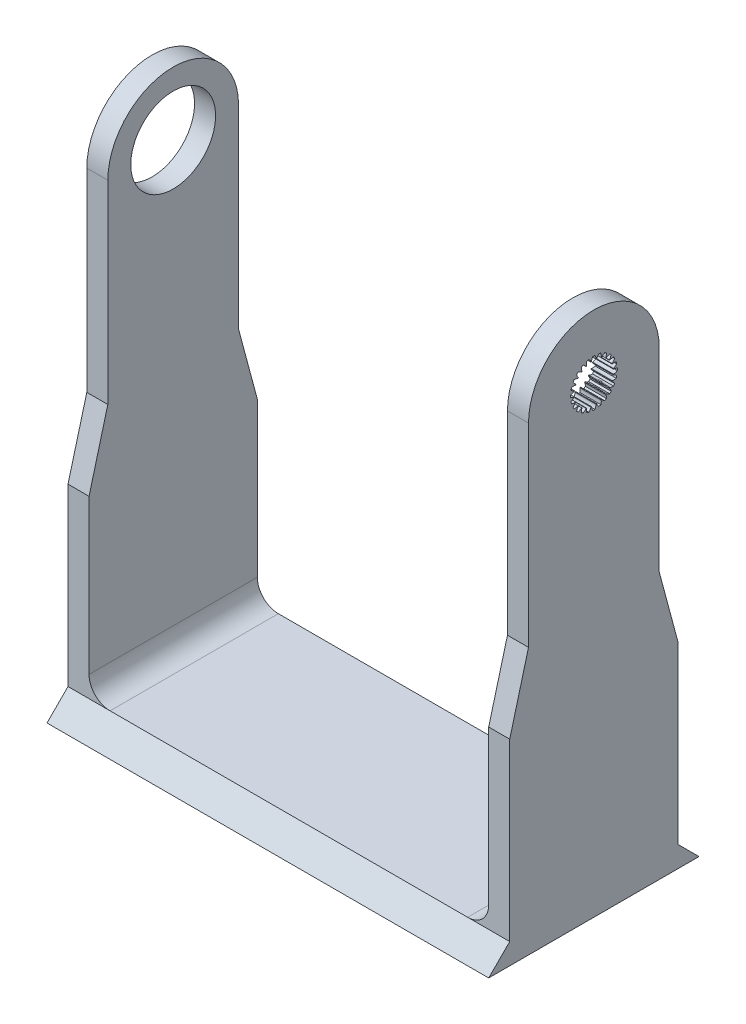
SolidWorks part; units mm, degrees
ref_plane "Front Plane" through (0, 0, 0) normal (0, 0, 1) x (1, 0, 0)
ref_plane "Top Plane" through (0, 0, 0) normal (0, 1, 0) x (1, 0, 0)
ref_plane "Right Plane" through (0, 0, 0) normal (1, 0, 0) x (0, 0, -1)
sketch "Sketch1" plane through (0, 0, 0) normal (0, 1, 0) x (1, 0, 0)
  line L1 (-31.5, -15) -> (31.5, -15)
  line L2 (-31.5, -15) -> (-31.5, 15)
  line L3 (-31.5, 15) -> (31.5, 15)
  line L4 (31.5, -15) -> (31.5, 15)
  point P4 (0, 15)
  point P6 (31.5, 0)
  dimension "D1" = 63
  dimension "D2" = 30
extrude "Boss-Extrude1" add sketch "Sketch1" along normal blind 3
sketch "Sketch2" plane through (0, 3, 0) normal (0, 1, 0) x (1, 0, 0)
  line L0 (-31.5, 15) -> (-31.5, -15) construction
  line L1 (-31.5, -12) -> (-28.5, -12)
  line L2 (-31.5, -12) -> (-31.5, 12)
  line L3 (-31.5, 12) -> (-28.5, 12)
  line L4 (-28.5, -12) -> (-28.5, 12)
  line L5 (31.5, -15) -> (31.5, 15) construction
  line L6 (31.5, -12) -> (28.5, -12)
  line L7 (31.5, -12) -> (31.5, 12)
  line L8 (31.5, 12) -> (28.5, 12)
  line L9 (28.5, -12) -> (28.5, 12)
  line L10 (31.5, 15) -> (-31.5, 15) construction
  line L11 (-31.5, -15) -> (31.5, -15) construction
  dimension "D1" = 3
  dimension "D2" = 3
  dimension "D3" = 3
  dimension "D4" = 3
  dimension "D5" = 3
  dimension "D6" = 3
extrude "Boss-Extrude2" add sketch "Sketch2" along normal blind 75
sketch "Sketch3" plane through (31.5, 0, 0) normal (1, 0, 0) x (0, 0, -1)
  line L0 (-15, 0) -> (15, 0) construction
  line L1 (-12, 78) -> (12, 78) construction
  line L2 (0, 13) -> (12, 13) construction
  line L3 (12, 78) -> (12, 3) construction
  line L4 (0, 13) -> (0, 66) construction
  line B0 (-2.5678, 64.8835) -> (-2.5895, 64.8732)
  line B1 (-2.2706, 64.3209) -> (-2.2508, 64.3345)
  line B2 (-2.1913, 64.257) -> (-2.2096, 64.2413)
  line B3 (-1.7587, 63.7904) -> (-1.743, 63.8087)
  line B4 (-1.6655, 63.7492) -> (-1.6791, 63.7294)
  line B5 (-1.1268, 63.4105) -> (-1.1165, 63.4322)
  line B6 (-1.0262, 63.3948) -> (-1.0342, 63.3722)
  line B7 (-0.4182, 63.2071) -> (-0.4138, 63.2308)
  line B8 (-0.317, 63.218) -> (-0.3189, 63.194)
  line B9 (0.3189, 63.194) -> (0.317, 63.218)
  line B10 (0.4138, 63.2308) -> (0.4182, 63.2071)
  line B11 (1.0342, 63.3722) -> (1.0262, 63.3948)
  line B12 (1.1165, 63.4322) -> (1.1268, 63.4105)
  line B13 (1.6791, 63.7294) -> (1.6655, 63.7492)
  line B14 (1.743, 63.8087) -> (1.7587, 63.7904)
  line B15 (2.2096, 64.2413) -> (2.1913, 64.257)
  line B16 (2.2508, 64.3345) -> (2.2706, 64.3209)
  line B17 (2.5895, 64.8732) -> (2.5678, 64.8835)
  line B18 (2.6052, 64.9738) -> (2.6278, 64.9658)
  line B19 (2.7929, 65.5818) -> (2.7692, 65.5862)
  line B20 (2.782, 65.683) -> (2.806, 65.6811)
  line B21 (2.806, 66.3189) -> (2.782, 66.317)
  line B22 (2.7692, 66.4138) -> (2.7929, 66.4182)
  line B23 (2.6278, 67.0342) -> (2.6052, 67.0262)
  line B24 (2.5678, 67.1165) -> (2.5895, 67.1268)
  line B25 (2.2706, 67.6791) -> (2.2508, 67.6655)
  line B26 (2.1913, 67.743) -> (2.2096, 67.7587)
  line B27 (1.7587, 68.2096) -> (1.743, 68.1913)
  line B28 (1.6655, 68.2508) -> (1.6791, 68.2706)
  line B29 (1.1268, 68.5895) -> (1.1165, 68.5678)
  line B30 (1.0262, 68.6052) -> (1.0342, 68.6278)
  line B31 (0.4182, 68.7929) -> (0.4138, 68.7692)
  line B32 (0.317, 68.782) -> (0.3189, 68.806)
  line B33 (-0.3189, 68.806) -> (-0.317, 68.782)
  line B34 (-0.4138, 68.7692) -> (-0.4182, 68.7929)
  line B35 (-1.0342, 68.6278) -> (-1.0262, 68.6052)
  line B36 (-1.1165, 68.5678) -> (-1.1268, 68.5895)
  line B37 (-1.6791, 68.2706) -> (-1.6655, 68.2508)
  line B38 (-1.743, 68.1913) -> (-1.7587, 68.2096)
  line B39 (-2.2096, 67.7587) -> (-2.1913, 67.743)
  line B40 (-2.2508, 67.6655) -> (-2.2706, 67.6791)
  line B41 (-2.5895, 67.1268) -> (-2.5678, 67.1165)
  line B42 (-2.6052, 67.0262) -> (-2.6278, 67.0342)
  line B43 (-2.7929, 66.4182) -> (-2.7692, 66.4138)
  line B44 (-2.782, 66.317) -> (-2.806, 66.3189)
  line B45 (-2.806, 65.6811) -> (-2.782, 65.683)
  line B46 (-2.7692, 65.5862) -> (-2.7929, 65.5818)
  line B47 (-2.6278, 64.9658) -> (-2.6052, 64.9738)
  arc B48 (-2.6052, 64.9738) -> (-2.5678, 64.8835) centre (0, 66) ccw
  arc B49 (-2.9635, 64.4594) -> (-2.8159, 64.2038) centre (0, 66) ccw
  arc B50 (-2.2508, 64.3345) -> (-2.1913, 64.257) centre (0, 66) ccw
  arc B51 (-2.4638, 63.7449) -> (-2.2551, 63.5362) centre (0, 66) ccw
  arc B52 (-1.743, 63.8087) -> (-1.6655, 63.7492) centre (0, 66) ccw
  arc B53 (-1.7962, 63.1841) -> (-1.5406, 63.0365) centre (0, 66) ccw
  arc B54 (-1.1165, 63.4322) -> (-1.0262, 63.3948) centre (0, 66) ccw
  arc B55 (-1.0062, 62.8152) -> (-0.7211, 62.7388) centre (0, 66) ccw
  arc B56 (-0.4138, 63.2308) -> (-0.317, 63.218) centre (0, 66) ccw
  arc B57 (-0.1476, 62.6633) -> (0.1476, 62.6633) centre (0, 66) ccw
  arc B58 (0.317, 63.218) -> (0.4138, 63.2308) centre (0, 66) ccw
  arc B59 (0.7211, 62.7388) -> (1.0062, 62.8152) centre (0, 66) ccw
  arc B60 (1.0262, 63.3948) -> (1.1165, 63.4322) centre (0, 66) ccw
  arc B61 (1.5406, 63.0365) -> (1.7962, 63.1841) centre (0, 66) ccw
  arc B62 (1.6655, 63.7492) -> (1.743, 63.8087) centre (0, 66) ccw
  arc B63 (2.2551, 63.5362) -> (2.4638, 63.7449) centre (0, 66) ccw
  arc B64 (2.1913, 64.257) -> (2.2508, 64.3345) centre (0, 66) ccw
  arc B65 (2.8159, 64.2038) -> (2.9635, 64.4594) centre (0, 66) ccw
  arc B66 (2.5678, 64.8835) -> (2.6052, 64.9738) centre (0, 66) ccw
  arc B67 (3.1848, 64.9938) -> (3.2612, 65.2789) centre (0, 66) ccw
  arc B68 (2.7692, 65.5862) -> (2.782, 65.683) centre (0, 66) ccw
  arc B69 (3.3367, 65.8524) -> (3.3367, 66.1476) centre (0, 66) ccw
  arc B70 (2.782, 66.317) -> (2.7692, 66.4138) centre (0, 66) ccw
  arc B71 (3.2612, 66.7211) -> (3.1848, 67.0062) centre (0, 66) ccw
  arc B72 (2.6052, 67.0262) -> (2.5678, 67.1165) centre (0, 66) ccw
  arc B73 (2.9635, 67.5406) -> (2.8159, 67.7962) centre (0, 66) ccw
  arc B74 (2.2508, 67.6655) -> (2.1913, 67.743) centre (0, 66) ccw
  arc B75 (2.4638, 68.2551) -> (2.2551, 68.4638) centre (0, 66) ccw
  arc B76 (1.743, 68.1913) -> (1.6655, 68.2508) centre (0, 66) ccw
  arc B77 (1.7962, 68.8159) -> (1.5406, 68.9635) centre (0, 66) ccw
  arc B78 (1.1165, 68.5678) -> (1.0262, 68.6052) centre (0, 66) ccw
  arc B79 (1.0062, 69.1848) -> (0.7211, 69.2612) centre (0, 66) ccw
  arc B80 (0.4138, 68.7692) -> (0.317, 68.782) centre (0, 66) ccw
  arc B81 (0.1476, 69.3367) -> (-0.1476, 69.3367) centre (0, 66) ccw
  arc B82 (-0.317, 68.782) -> (-0.4138, 68.7692) centre (0, 66) ccw
  arc B83 (-0.7211, 69.2612) -> (-1.0062, 69.1848) centre (0, 66) ccw
  arc B84 (-1.0262, 68.6052) -> (-1.1165, 68.5678) centre (0, 66) ccw
  arc B85 (-1.5406, 68.9635) -> (-1.7962, 68.8159) centre (0, 66) ccw
  arc B86 (-1.6655, 68.2508) -> (-1.743, 68.1913) centre (0, 66) ccw
  arc B87 (-2.2551, 68.4638) -> (-2.4638, 68.2551) centre (0, 66) ccw
  arc B88 (-2.1913, 67.743) -> (-2.2508, 67.6655) centre (0, 66) ccw
  arc B89 (-2.8159, 67.7962) -> (-2.9635, 67.5406) centre (0, 66) ccw
  arc B90 (-2.5678, 67.1165) -> (-2.6052, 67.0262) centre (0, 66) ccw
  arc B91 (-3.1848, 67.0062) -> (-3.2612, 66.7211) centre (0, 66) ccw
  arc B92 (-2.7692, 66.4138) -> (-2.782, 66.317) centre (0, 66) ccw
  arc B93 (-3.3367, 66.1476) -> (-3.3367, 65.8524) centre (0, 66) ccw
  arc B94 (-2.782, 65.683) -> (-2.7692, 65.5862) centre (0, 66) ccw
  arc B95 (-3.2612, 65.2789) -> (-3.1848, 64.9938) centre (0, 66) ccw
  spline B96 degree 3 poles (-2.5895, 64.8732) (-2.6723, 64.8269) (-2.7395, 64.7607) (-2.862, 64.6182) (-2.9137, 64.5392) (-2.9635, 64.4594) knots 0 0 0 0 0.5 0.5 1 1 1 1
  spline B97 degree 3 poles (-2.8159, 64.2038) (-2.722, 64.2071) (-2.628, 64.2123) (-2.4433, 64.2471) (-2.3516, 64.2726) (-2.2706, 64.3209) knots 0 0 0 0 0.5 0.5 1 1 1 1
  spline B98 degree 3 poles (-2.2096, 64.2413) (-2.2776, 64.1752) (-2.3254, 64.0939) (-2.4068, 63.9245) (-2.4363, 63.8349) (-2.4638, 63.7449) knots 0 0 0 0 0.5 0.5 1 1 1 1
  spline B99 degree 3 poles (-2.2551, 63.5362) (-2.1652, 63.5637) (-2.0757, 63.5931) (-1.9063, 63.6744) (-1.8244, 63.7228) (-1.7587, 63.7904) knots 0 0 0 0 0.5 0.5 1 1 1 1
  spline B100 degree 3 poles (-1.6791, 63.7294) (-1.7277, 63.6479) (-1.7529, 63.557) (-1.7877, 63.3723) (-1.7929, 63.2781) (-1.7962, 63.1841) knots 0 0 0 0 0.5 0.5 1 1 1 1
  spline B101 degree 3 poles (-1.5406, 63.0365) (-1.4609, 63.0863) (-1.382, 63.1378) (-1.2395, 63.2603) (-1.1728, 63.3282) (-1.1268, 63.4105) knots 0 0 0 0 0.5 0.5 1 1 1 1
  spline B102 degree 3 poles (-1.0342, 63.3722) (-1.06, 63.2809) (-1.0608, 63.1866) (-1.0466, 62.9992) (-1.0273, 62.9068) (-1.0062, 62.8152) knots 0 0 0 0 0.5 0.5 1 1 1 1
  spline B103 degree 3 poles (-0.7211, 62.7388) (-0.657, 62.8075) (-0.5942, 62.8777) (-0.4881, 63.0328) (-0.4414, 63.1157) (-0.4182, 63.2071) knots 0 0 0 0 0.5 0.5 1 1 1 1
  spline B104 degree 3 poles (-0.3189, 63.194) (-0.3202, 63.0992) (-0.2965, 63.0079) (-0.2343, 62.8305) (-0.1917, 62.7463) (-0.1476, 62.6633) knots 0 0 0 0 0.5 0.5 1 1 1 1
  spline B105 degree 3 poles (0.1476, 62.6633) (0.1917, 62.7462) (0.2342, 62.8303) (0.2965, 63.0076) (0.3202, 63.0998) (0.3189, 63.194) knots 0 0 0 0 0.5 0.5 1 1 1 1
  spline B106 degree 3 poles (0.4182, 63.2071) (0.4415, 63.1152) (0.488, 63.0331) (0.594, 62.8779) (0.6569, 62.8075) (0.7211, 62.7388) knots 0 0 0 0 0.5 0.5 1 1 1 1
  spline B107 degree 3 poles (1.0062, 62.8152) (1.0273, 62.9067) (1.0466, 62.9989) (1.0608, 63.1863) (1.0599, 63.2815) (1.0342, 63.3722) knots 0 0 0 0 0.5 0.5 1 1 1 1
  spline B108 degree 3 poles (1.1268, 63.4105) (1.1731, 63.3277) (1.2393, 63.2605) (1.3818, 63.138) (1.4608, 63.0863) (1.5406, 63.0365) knots 0 0 0 0 0.5 0.5 1 1 1 1
  spline B109 degree 3 poles (1.7962, 63.1841) (1.7929, 63.278) (1.7877, 63.372) (1.7529, 63.5567) (1.7274, 63.6484) (1.6791, 63.7294) knots 0 0 0 0 0.5 0.5 1 1 1 1
  spline B110 degree 3 poles (1.7587, 63.7904) (1.8248, 63.7224) (1.9061, 63.6746) (2.0755, 63.5932) (2.1651, 63.5637) (2.2551, 63.5362) knots 0 0 0 0 0.5 0.5 1 1 1 1
  spline B111 degree 3 poles (2.4638, 63.7449) (2.4363, 63.8348) (2.4069, 63.9243) (2.3256, 64.0937) (2.2772, 64.1756) (2.2096, 64.2413) knots 0 0 0 0 0.5 0.5 1 1 1 1
  spline B112 degree 3 poles (2.2706, 64.3209) (2.3521, 64.2723) (2.443, 64.2471) (2.6277, 64.2123) (2.7219, 64.2071) (2.8159, 64.2038) knots 0 0 0 0 0.5 0.5 1 1 1 1
  spline B113 degree 3 poles (2.9635, 64.4594) (2.9137, 64.5391) (2.8622, 64.618) (2.7397, 64.7605) (2.6718, 64.8272) (2.5895, 64.8732) knots 0 0 0 0 0.5 0.5 1 1 1 1
  spline B114 degree 3 poles (2.6278, 64.9658) (2.7191, 64.94) (2.8134, 64.9392) (3.0008, 64.9534) (3.0932, 64.9727) (3.1848, 64.9938) knots 0 0 0 0 0.5 0.5 1 1 1 1
  spline B115 degree 3 poles (3.2612, 65.2789) (3.1925, 65.343) (3.1223, 65.4058) (2.9672, 65.5119) (2.8843, 65.5586) (2.7929, 65.5818) knots 0 0 0 0 0.5 0.5 1 1 1 1
  spline B116 degree 3 poles (2.806, 65.6811) (2.9008, 65.6798) (2.9921, 65.7035) (3.1695, 65.7657) (3.2537, 65.8083) (3.3367, 65.8524) knots 0 0 0 0 0.5 0.5 1 1 1 1
  spline B117 degree 3 poles (3.3367, 66.1476) (3.2538, 66.1917) (3.1697, 66.2342) (2.9924, 66.2965) (2.9002, 66.3202) (2.806, 66.3189) knots 0 0 0 0 0.5 0.5 1 1 1 1
  spline B118 degree 3 poles (2.7929, 66.4182) (2.8848, 66.4415) (2.9669, 66.488) (3.1221, 66.594) (3.1925, 66.6569) (3.2612, 66.7211) knots 0 0 0 0 0.5 0.5 1 1 1 1
  spline B119 degree 3 poles (3.1848, 67.0062) (3.0933, 67.0273) (3.0011, 67.0466) (2.8137, 67.0608) (2.7185, 67.0599) (2.6278, 67.0342) knots 0 0 0 0 0.5 0.5 1 1 1 1
  spline B120 degree 3 poles (2.5895, 67.1268) (2.6723, 67.1731) (2.7395, 67.2393) (2.862, 67.3818) (2.9137, 67.4608) (2.9635, 67.5406) knots 0 0 0 0 0.5 0.5 1 1 1 1
  spline B121 degree 3 poles (2.8159, 67.7962) (2.722, 67.7929) (2.628, 67.7877) (2.4433, 67.7529) (2.3516, 67.7274) (2.2706, 67.6791) knots 0 0 0 0 0.5 0.5 1 1 1 1
  spline B122 degree 3 poles (2.2096, 67.7587) (2.2776, 67.8248) (2.3254, 67.9061) (2.4068, 68.0755) (2.4363, 68.1651) (2.4638, 68.2551) knots 0 0 0 0 0.5 0.5 1 1 1 1
  spline B123 degree 3 poles (2.2551, 68.4638) (2.1652, 68.4363) (2.0757, 68.4069) (1.9063, 68.3256) (1.8244, 68.2772) (1.7587, 68.2096) knots 0 0 0 0 0.5 0.5 1 1 1 1
  spline B124 degree 3 poles (1.6791, 68.2706) (1.7277, 68.3521) (1.7529, 68.443) (1.7877, 68.6277) (1.7929, 68.7219) (1.7962, 68.8159) knots 0 0 0 0 0.5 0.5 1 1 1 1
  spline B125 degree 3 poles (1.5406, 68.9635) (1.4609, 68.9137) (1.382, 68.8622) (1.2395, 68.7397) (1.1728, 68.6718) (1.1268, 68.5895) knots 0 0 0 0 0.5 0.5 1 1 1 1
  spline B126 degree 3 poles (1.0342, 68.6278) (1.06, 68.7191) (1.0608, 68.8134) (1.0466, 69.0008) (1.0273, 69.0932) (1.0062, 69.1848) knots 0 0 0 0 0.5 0.5 1 1 1 1
  spline B127 degree 3 poles (0.7211, 69.2612) (0.657, 69.1925) (0.5942, 69.1223) (0.4881, 68.9672) (0.4414, 68.8843) (0.4182, 68.7929) knots 0 0 0 0 0.5 0.5 1 1 1 1
  spline B128 degree 3 poles (0.3189, 68.806) (0.3202, 68.9008) (0.2965, 68.9921) (0.2343, 69.1695) (0.1917, 69.2537) (0.1476, 69.3367) knots 0 0 0 0 0.5 0.5 1 1 1 1
  spline B129 degree 3 poles (-0.1476, 69.3367) (-0.1917, 69.2538) (-0.2342, 69.1697) (-0.2965, 68.9924) (-0.3202, 68.9002) (-0.3189, 68.806) knots 0 0 0 0 0.5 0.5 1 1 1 1
  spline B130 degree 3 poles (-0.4182, 68.7929) (-0.4415, 68.8848) (-0.488, 68.9669) (-0.594, 69.1221) (-0.6569, 69.1925) (-0.7211, 69.2612) knots 0 0 0 0 0.5 0.5 1 1 1 1
  spline B131 degree 3 poles (-1.0062, 69.1848) (-1.0273, 69.0933) (-1.0466, 69.0011) (-1.0608, 68.8137) (-1.0599, 68.7185) (-1.0342, 68.6278) knots 0 0 0 0 0.5 0.5 1 1 1 1
  spline B132 degree 3 poles (-1.1268, 68.5895) (-1.1731, 68.6723) (-1.2393, 68.7395) (-1.3818, 68.862) (-1.4608, 68.9137) (-1.5406, 68.9635) knots 0 0 0 0 0.5 0.5 1 1 1 1
  spline B133 degree 3 poles (-1.7962, 68.8159) (-1.7929, 68.722) (-1.7877, 68.628) (-1.7529, 68.4433) (-1.7274, 68.3516) (-1.6791, 68.2706) knots 0 0 0 0 0.5 0.5 1 1 1 1
  spline B134 degree 3 poles (-1.7587, 68.2096) (-1.8248, 68.2776) (-1.9061, 68.3254) (-2.0755, 68.4068) (-2.1651, 68.4363) (-2.2551, 68.4638) knots 0 0 0 0 0.5 0.5 1 1 1 1
  spline B135 degree 3 poles (-2.4638, 68.2551) (-2.4363, 68.1652) (-2.4069, 68.0757) (-2.3256, 67.9063) (-2.2772, 67.8244) (-2.2096, 67.7587) knots 0 0 0 0 0.5 0.5 1 1 1 1
  spline B136 degree 3 poles (-2.2706, 67.6791) (-2.3521, 67.7277) (-2.443, 67.7529) (-2.6277, 67.7877) (-2.7219, 67.7929) (-2.8159, 67.7962) knots 0 0 0 0 0.5 0.5 1 1 1 1
  spline B137 degree 3 poles (-2.9635, 67.5406) (-2.9137, 67.4609) (-2.8622, 67.382) (-2.7397, 67.2395) (-2.6718, 67.1728) (-2.5895, 67.1268) knots 0 0 0 0 0.5 0.5 1 1 1 1
  spline B138 degree 3 poles (-2.6278, 67.0342) (-2.7191, 67.06) (-2.8134, 67.0608) (-3.0008, 67.0466) (-3.0932, 67.0273) (-3.1848, 67.0062) knots 0 0 0 0 0.5 0.5 1 1 1 1
  spline B139 degree 3 poles (-3.2612, 66.7211) (-3.1925, 66.657) (-3.1223, 66.5942) (-2.9672, 66.4881) (-2.8843, 66.4414) (-2.7929, 66.4182) knots 0 0 0 0 0.5 0.5 1 1 1 1
  spline B140 degree 3 poles (-2.806, 66.3189) (-2.9008, 66.3202) (-2.9921, 66.2965) (-3.1695, 66.2343) (-3.2537, 66.1917) (-3.3367, 66.1476) knots 0 0 0 0 0.5 0.5 1 1 1 1
  spline B141 degree 3 poles (-3.3367, 65.8524) (-3.2538, 65.8083) (-3.1697, 65.7658) (-2.9924, 65.7035) (-2.9002, 65.6798) (-2.806, 65.6811) knots 0 0 0 0 0.5 0.5 1 1 1 1
  spline B142 degree 3 poles (-2.7929, 65.5818) (-2.8848, 65.5585) (-2.9669, 65.512) (-3.1221, 65.406) (-3.1925, 65.3431) (-3.2612, 65.2789) knots 0 0 0 0 0.5 0.5 1 1 1 1
  spline B143 degree 3 poles (-3.1848, 64.9938) (-3.0933, 64.9727) (-3.0011, 64.9534) (-2.8137, 64.9392) (-2.7185, 64.9401) (-2.6278, 64.9658) knots 0 0 0 0 0.5 0.5 1 1 1 1
  dimension "D1" = 53
  dimension "D2" = 13
  dimension "D3" = 12
sketch_block_instance "Block2-1"
sketch_block "Block2"
extrude "Cut-Extrude1" cut sketch "Sketch3" against normal up to surface (3 mm away) up to face at (28.5, 40.5, 0)
sketch "Sketch4" plane through (-31.5, 0, 0) normal (-1, 0, 0) x (0, 0, 1)
  circle A0 centre (0, 66) radius 6.05
  dimension "D1" = 12.1
extrude "Cut-Extrude2" cut sketch "Sketch4" against normal up to surface (3 mm away) up to face at (-28.5, 40.5, 0)
sketch "Sketch5" plane through (31.5, 0, 0) normal (1, 0, 0) x (0, 0, -1)
  line L2 (-12, 3) -> (-12, 28)
  line L4 (-12, 78) -> (-12, 3) construction
  line L6 (-12, 28) -> (-9.3205, 38)
  line L11 (-9.3205, 38) -> (-9.3205, 65.7)
  line L12 (12, 3) -> (12, 28)
  line L13 (12, 78) -> (12, 3) construction
  line L14 (12, 28) -> (9.3205, 38)
  line L15 (9.3205, 38) -> (9.3205, 65.7)
  line L16 (-12, 28) -> (-12, 78)
  line L17 (-12, 78) -> (12, 78)
  line L18 (12, 78) -> (12, 28)
  line L19 (12, 78) -> (12, 28)
  arc A3 (-9.3205, 65.7) -> (9.3205, 65.7) centre (0, 65.7) cw
  dimension "D3" = 27.7
  dimension "D4" = 15
  dimension "D1" = 25
  dimension "D2" = 15
  dimension "D6" = 10
  dimension "D7" = 10
  dimension "D8" = 25
  dimension "D9" = 27.7
chamfer "Chamfer1" distance 3 angle 45 2 edges at (0, 3, -15) (0, 3, 15)
fillet "Fillet1" radius 3 2 edges at (-28.5, 3, 0) (28.5, 3, 0)
extrude "Cut-Extrude3" cut sketch "Sketch5" against normal blind 10 contours L11 A3 L15 L14 L18 L17 L16 L6
mirror "Mirror1" about plane through (0, 0, 0) normal (1, 0, 0) of "Cut-Extrude3"
